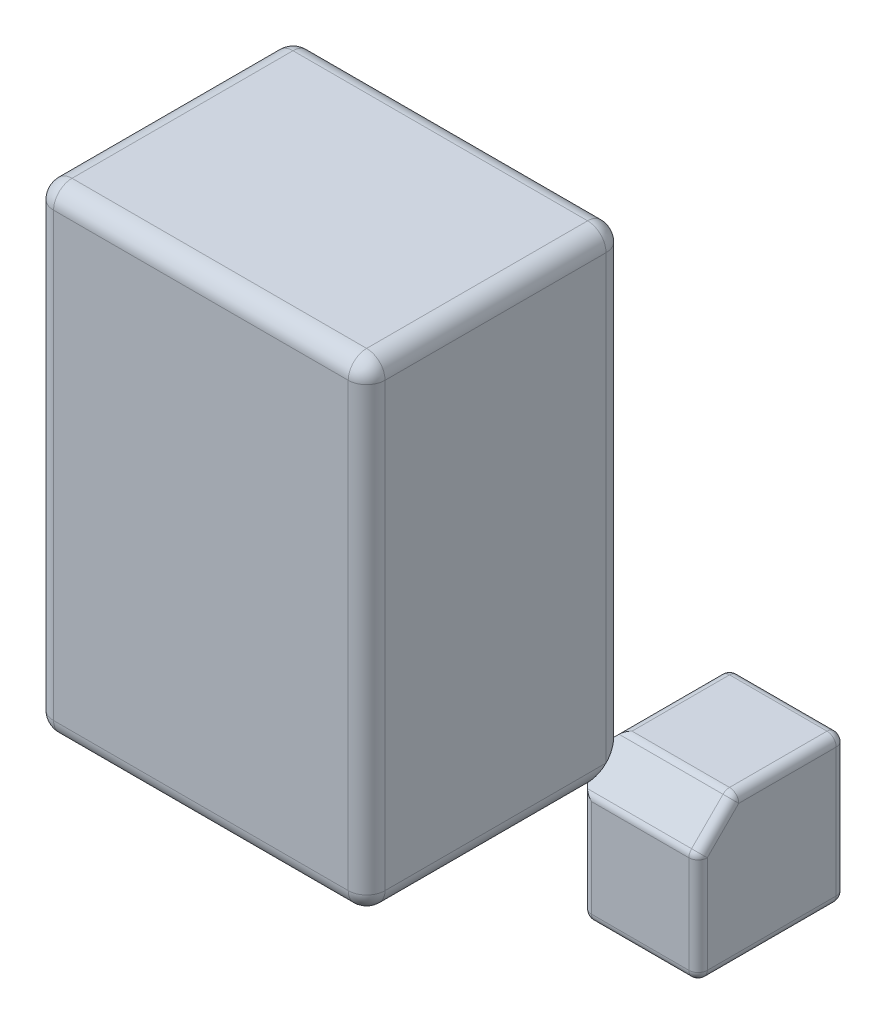
SolidWorks part; units mm, degrees
ref_plane "Front Plane" through (0, 0, 0) normal (0, 0, 1) x (1, 0, 0)
ref_plane "Top Plane" through (0, 0, 0) normal (0, 1, 0) x (1, 0, 0)
ref_plane "Right Plane" through (0, 0, 0) normal (1, 0, 0) x (0, 0, -1)
sketch "Sketch1" plane through (0, 0, 0) normal (0, 0, 1) x (1, 0, 0)
  line L1 (0, 0) -> (18, 0)
  line L2 (0, 0) -> (0, 26)
  line L3 (0, 26) -> (18, 26)
  line L4 (18, 0) -> (18, 26)
  dimension "D1" = 18
  dimension "D2" = 26
extrude "Boss-Extrude1" add sketch "Sketch1" along normal blind 14
sketch "Sketch2" plane through (0, 0, 0) normal (0, 0, -1) x (-1, 0, 0)
  line L0 (-18, 0) -> (-18, 26) construction
  line L1 (-16, 2) -> (-24, 2)
  line L2 (-16, 2) -> (-16, -6)
  line L3 (-16, -6) -> (-24, -6)
  line L4 (-24, 2) -> (-24, -6)
  line L5 (0, 0) -> (-18, 0) construction
  dimension "D1" = 2
  dimension "D2" = 2
  dimension "D3" = 8
  dimension "D4" = 8
shell "Shell1" thickness 1
extrude "Boss-Extrude3" add sketch "Sketch2" along normal blind 6 and the other way blind 2 contours L3 L4 L1 L2
chamfer "Chamfer2" distance 2 angle 45 3 edges at (21, 2, 2) (16, 2, -3) (16, -3, 2)
fillet "Fillet1" radius 1 12 edges at (0, 13, 0) (8, 0, 0) (18, 14, 0) (9, 26, 0) (9, 0, 14) (18, 13, 14) (9, 26, 14) (0, 26, 7) (18, 26, 7) (18, 0, 8) (0, 0, 7) (0, 13, 14)
fillet "Fillet2" radius 0.5 18 edges at (24, -6, -2) (20, -6, -6) (17, -6, 1) (21, -6, 2) (16, -6, -3) (16, -3, -6) (16, 0, -3) (16, -3, 0) (21, 0, 2) (17, 1, -6) (21, 2, -6) (24, 2, -3) (21, 2, 0) (18, 2, -3) (24, -3, 2) (24, -2, -6) (18, -3, 2) (24, 1, 1)
